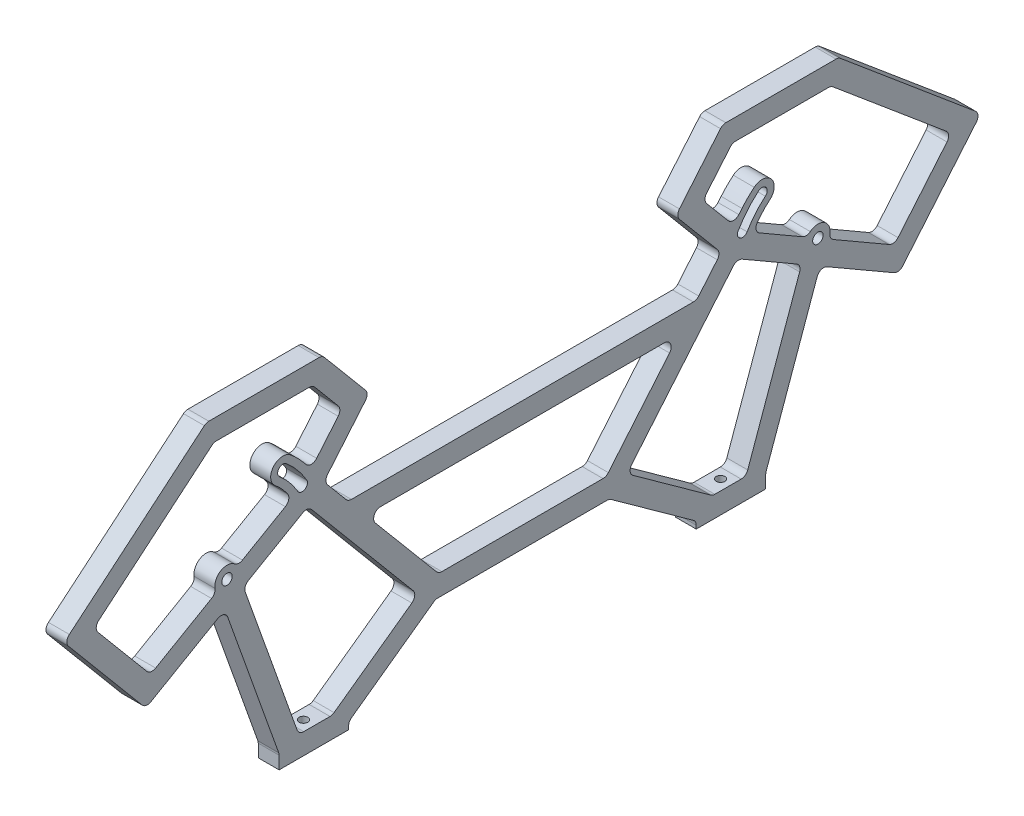
SolidWorks part; units mm, degrees
material "1060 Alloy"
ref_plane "Front Plane" through (0, 0, 0) normal (0, 0, 1) x (1, 0, 0)
ref_plane "Top Plane" through (0, 0, 0) normal (0, 1, 0) x (1, 0, 0)
ref_plane "Right Plane" through (0, 0, 0) normal (1, 0, 0) x (0, 0, -1)
sketch "Sketch1" plane through (0, 0, 0) normal (1, 0, 0) x (0, 0, -1)
  line L0 (65.8489, 71.0697) -> (85, 55) construction
  line L1 (50, 0) -> (70, 0)
  line L2 (131.2449, 61.8851) -> (104.8907, 30.4773) construction
  line L3 (131.2449, 61.8851) -> (73.0256, 110.737) construction
  line L4 (104.8907, 30.4773) -> (46.6713, 79.3292) construction
  line L5 (73.0256, 110.737) -> (46.6713, 79.3292) construction
  line L6 (50, 0) -> (50, 2)
  line L7 (50, 2) -> (25, 20)
  line L8 (25, 20) -> (0, 20)
  line L9 (120.803, 46.5093) -> (61.0516, 96.6468) construction
  line L10 (0, 20) -> (0, 26)
  line L11 (0, 26) -> (24.1147, 26)
  line L12 (24.1147, 26) -> (45.0922, 51)
  line L13 (45.0922, 51) -> (0, 51)
  line L14 (65.0961, 75.6176) -> (85.3963, 58.5837) construction
  line L15 (65.0961, 75.6176) -> (82.13, 95.9178) construction
  line L16 (85.3963, 58.5837) -> (102.4301, 78.8839) construction
  line L17 (0, 51) -> (0, 57)
  line L18 (82.13, 95.9178) -> (102.4301, 78.8839) construction
  line L19 (0, 57) -> (50.1268, 57)
  line L20 (106.773, 98) -> (-82.0096, 98) construction
  line L21 (44.087, 80.9165) -> (57.141, 65.3592)
  line L22 (68.9303, 74.1511) -> (85, 55) construction
  line L23 (85, 55) -> (63.3494, 67.5) construction
  line L24 (30.0596, 23.7505) -> (61.7373, 61.5025)
  line L25 (61.7373, 61.5025) -> (80.3101, 50.7795)
  line L26 (80.3101, 50.7795) -> (64.3431, 6)
  line L27 (64.3431, 6) -> (54.7131, 6)
  line L28 (54.7131, 6) -> (30.0596, 23.7505)
  line L29 (70, 0) -> (70, 4)
  line L30 (70, 4) -> (85.5926, 47.7296)
  line L31 (85.5926, 47.7296) -> (108.3447, 34.5937)
  line L32 (108.3447, 34.5937) -> (131.8877, 62.6512)
  line L33 (131.8877, 62.6512) -> (90.9524, 97)
  line L34 (90.9524, 97) -> (57.5826, 97)
  line L35 (132, 92.0287) -> (132, -4.4174) construction
  line L36 (60.3805, 91) -> (51.9194, 80.9165)
  line L37 (140, 92.0287) -> (140, -4.4174) construction
  line L38 (88.0311, 53.25) -> (106.9846, 42.3072)
  line L39 (66.3805, 65.75) -> (81.9689, 56.75)
  line L42 (106.9846, 42.3072) -> (123.4347, 61.9116)
  line L43 (123.4347, 61.9116) -> (88.7686, 91)
  line L44 (88.7686, 91) -> (60.3805, 91)
  line L46 (57.5826, 97) -> (44.087, 80.9165)
  line L47 (61.7373, 61.5025) -> (59.4392, 63.4309) construction
  line L48 (59.4392, 63.4309) -> (65.8489, 71.0697) construction
  line L49 (85, 55) -> (75.9689, 29.6723) construction
  line L50 (57.141, 65.3592) -> (50.1268, 57)
  line L51 (51.9194, 80.9165) -> (60.7309, 70.4153)
  line L52 (60.7309, 70.4153) -> (63.1677, 73.3194)
  circle A0 centre (85, 55) radius 1.5
  circle A1 centre (65.8489, 71.0697) radius 1.5 construction
  circle A2 centre (85, 55) radius 3 construction
  circle A3 centre (65.8489, 71.0697) radius 3 construction
  arc A4 (63.3494, 67.5) -> (68.9303, 74.1511) centre (85, 55) cw construction
  arc A5 (67.9661, 75.3002) -> (62.0503, 68.25) centre (85, 55) ccw
  arc A6 (69.8945, 73.002) -> (64.6484, 66.75) centre (85, 55) ccw
  arc A7 (69.8945, 73.002) -> (67.9661, 75.3002) centre (68.9303, 74.1511) ccw
  arc A8 (62.0503, 68.25) -> (64.6484, 66.75) centre (63.3494, 67.5) ccw
  arc A9 (71.1801, 71.47) -> (66.3805, 65.75) centre (85, 55) ccw
  arc A10 (63.1677, 73.3194) -> (66.6806, 76.8323) centre (85, 55) cw
  arc A11 (66.6806, 76.8323) -> (71.1801, 71.47) centre (68.9303, 74.1511) cw
  arc A12 (81.9689, 56.75) -> (88.0311, 53.25) centre (85, 55) cw
  point P25 (65.8489, 71.0697)
  dimension "D14" = 3
  dimension "D16" = 1.5
  dimension "D21" = 2
  dimension "D29" = 6
  dimension "D30" = 2
  dimension "D19" = 3.5
  dimension "D1" = 6
  dimension "D2" = 31
  dimension "D3" = 3
  dimension "D4" = 41
  dimension "D5" = 20
  dimension "D6" = 55
  dimension "D7" = 85
  dimension "D8" = 25
  dimension "D9" = 20
  dimension "D10" = 40
  dimension "D11" = 50
  dimension "D12" = 26.5
  dimension "D13" = 26.5
  dimension "D15" = 3.5
  dimension "D17" = 10
  dimension "D18" = 6
  dimension "D20" = 132
  dimension "D22" = 3
  dimension "D23" = 3
  dimension "D24" = 140
  dimension "D25" = 6
  dimension "D26" = 5
  dimension "D27" = 1
  dimension "D28" = 98
  dimension "D31" = 6
  dimension "D32" = 6
  dimension "D33" = 6
  dimension "D34" = 6
  dimension "D35" = 6
  dimension "D36" = 6
  dimension "D37" = 3
  dimension "D38" = 6
  dimension "D39" = 6
  dimension "D40" = 20
  dimension "D41" = 6
  dimension "D42" = 25
  dimension "D43" = 6
  dimension "D44" = 2
  dimension "D45" = 4
  dimension "D46" = 25
extrude "Boss-Extrude1" add sketch "Sketch1" along normal blind 6
hole_wizard "Tap Drill for M3 Tap1" positions "Sketch3" profile "Sketch2" hole size "M3" standard "ISO"
sketch "Sketch3" plane through (0, 0, 0) normal (0, -1, 0) x (-1, 0, 0)
  line L1 (-6, 50) -> (-6, 70) construction
  line L2 (-6, 70) -> (0, 70) construction
  point P0 (-3, 60)
  dimension "D1" = 10
  dimension "D2" = 3
sketch "Sketch2" plane through (3, 0, -60) normal (1, 0, 0) x (0, 0, -1)
  line L0 (0, 0) -> (0, 10.7511)
  line L1 (0, 10.7511) -> (1.25, 10)
  line L2 (1.25, 10) -> (1.25, 0)
  line L5 (1.25, 0) -> (0, 0)
  line L10 (0, 10.7511) -> (-1.25, 10) construction
  line L11 (0, -6.35) -> (0, 107.95) construction
  dimension "Hole Dia." = 2.5
  dimension "Hole Depth" = 10
  dimension "Drill Angle" = 118
fillet "Fillet1" radius 2 27 edges at (3, 65.75, -66.3805) (3, 56.75, -81.9689) (3, 53.25, -88.0311) (3, 42.3072, -106.9846) (3, 61.9116, -123.4347) (3, 91, -88.7686) (3, 91, -60.3805) (3, 80.9165, -51.9194) (3, 70.4153, -60.7309) (3, 57, -50.1268) (3, 80.9165, -44.087) (3, 97, -57.5826) (3, 97, -90.9524) (3, 62.6512, -131.8877) (3, 34.5937, -108.3447) (3, 47.7296, -85.5926) (3, 4, -70) (3, 2, -50) (3, 20, -25) (3, 23.7505, -30.0596) (3, 6, -54.7131) (3, 6, -64.3431) (3, 50.7795, -80.3101) (3, 61.5025, -61.7373) (3, 26, -24.1147) (3, 65.3592, -57.141) (3, 51, -45.0922)
mirror "Mirror1" about plane through (0, 0, 0) normal (0, 0, 1) of "Fillet1", "Tap Drill for M3 Tap1", "Boss-Extrude1"
